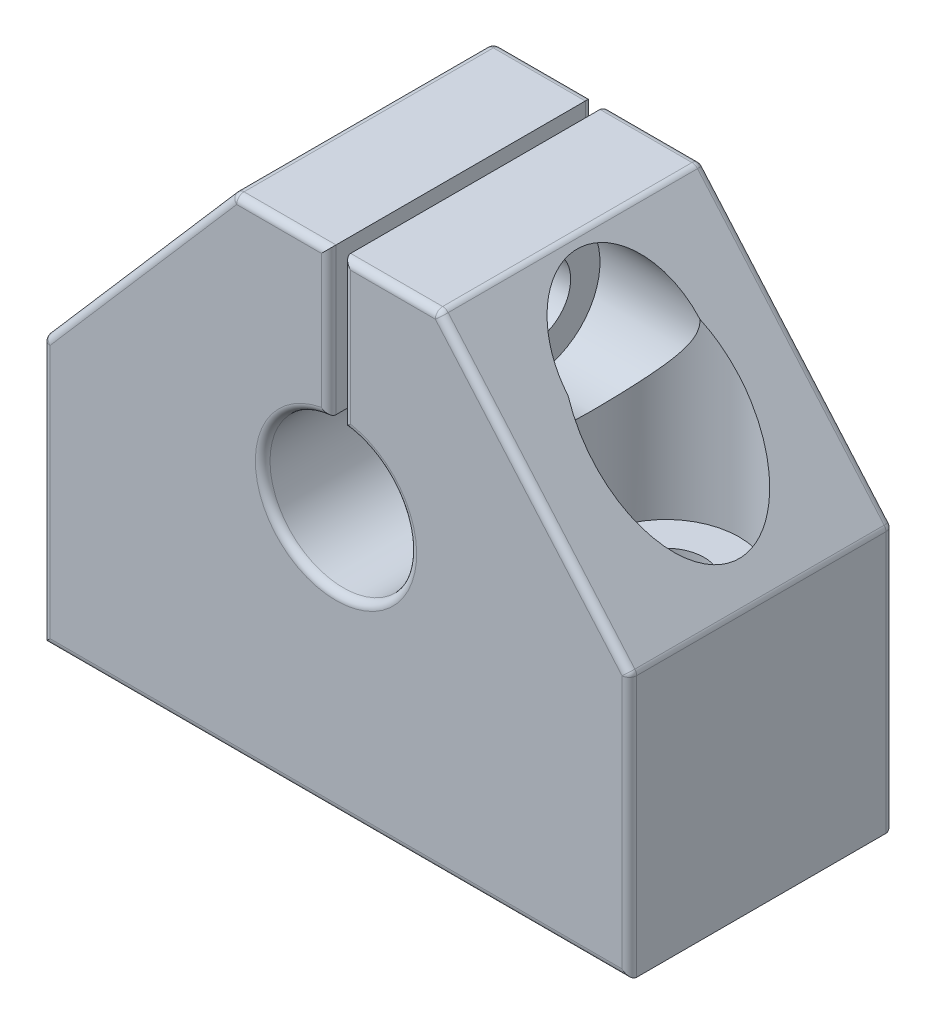
SolidWorks part; units mm, degrees
material "1060 Alloy"
ref_plane "Front Plane" through (0, 0, 0) normal (0, 0, 1) x (1, 0, 0)
ref_plane "Top Plane" through (0, 0, 0) normal (0, 1, 0) x (1, 0, 0)
ref_plane "Right Plane" through (0, 0, 0) normal (1, 0, 0) x (0, 0, -1)
sketch "Sketch1" plane through (0, 0, 0) normal (0, 0, 1) x (1, 0, 0)
  line L0 (20, 0) -> (20, 33) construction
  line L1 (0, 0) -> (40, 0)
  line L2 (0, 0) -> (0, 18)
  line L4 (40, 0) -> (40, 18)
  line L5 (13, 33) -> (0, 18)
  line L6 (13, 33) -> (27, 33)
  line L7 (27, 33) -> (40, 18)
  dimension "D1" = 18
  dimension "D2" = 40
  dimension "D3" = 33
  dimension "D5" = 7
extrude "Boss-Extrude1" add sketch "Sketch1" along normal blind 9 and the other way blind 9
sketch "Sketch2" plane through (0, 0, 9) normal (0, 0, 1) x (1, 0, 0)
  line L0 (20, 0) -> (20, 33) construction
  line L1 (0, 0) -> (40, 0) construction
  line L2 (27, 33) -> (13, 33) construction
  circle A0 centre (20, 18) radius 5
  dimension "D1" = 10
  dimension "D2" = 18
extrude "Cut-Extrude1" cut sketch "Sketch2" against normal through all
sketch "Sketch4" plane through (0, 0, 0) normal (0, 0, 1) x (1, 0, 0)
  line L0 (20, 0) -> (33.5, 0) construction
  line L1 (0, 0) -> (40, 0) construction
  dimension "D1" = 13.5
sketch "Sketch5" plane through (0, 0, 0) normal (0, -1, 0) x (-1, 0, 0)
  circle A0 centre (-33.5, 0) radius 2.6
  dimension "D1" = 5.2
extrude "Cut-Extrude2" cut sketch "Sketch5" against normal blind 16
sketch "Sketch7" plane through (0, 16, 0) normal (0, -1, 0) x (-1, 0, 0)
  circle A0 centre (-33.5, 0) radius 5
  dimension "D1" = 10
extrude "Cut-Extrude3" cut sketch "Sketch7" against normal through all
ref_plane "Plane1" through (20, 0, 0) normal (1, 0, 0) x (0, 0, -1)
mirror "Mirror1" about plane through (20, 0, 0) normal (1, 0, 0) of "Cut-Extrude2", "Cut-Extrude3"
sketch "Sketch9" plane through (0, 0, 9) normal (0, 0, 1) x (1, 0, 0)
  line L0 (20, 33) -> (20, 23) construction
  line L1 (27, 33) -> (13, 33) construction
  line L2 (20, -9.9) -> (20, 9.9) construction
  line L4 (19.5, 33.0251) -> (20.5, 33.0251)
  line L5 (19.5, 33.0251) -> (19.5, 22.9749)
  line L6 (19.5, 22.9749) -> (20.5, 22.9749)
  line L7 (20.5, 33.0251) -> (20.5, 22.9749)
  line L8 (19.5, 33.0251) -> (20.5, 22.9749) construction
  line L9 (19.5, 22.9749) -> (20.5, 33.0251) construction
  circle A0 centre (20, 18) radius 5 construction
  point P8 (20, 28)
  dimension "D1" = 1
extrude "Cut-Extrude4" cut sketch "Sketch9" against normal through all
sketch "Sketch10" plane through (19.5, 0, 0) normal (1, 0, 0) x (0, 0, -1)
  line L0 (0, 33) -> (0, 22.9749) construction
  line L1 (9, 33) -> (-9, 33) construction
  line L2 (9, 22.9749) -> (-9, 22.9749) construction
  circle A0 centre (0, 27.9875) radius 2.5
  dimension "D1" = 5
extrude "Cut-Extrude5" cut sketch "Sketch10" against normal through all and the other way blind 5
sketch "Sketch11" plane through (24.5, 0, 0) normal (-1, 0, 0) x (0, 0, 1)
  circle A0 centre (0, 27.9875) radius 4.5
  dimension "D1" = 9
extrude "Cut-Extrude6" cut sketch "Sketch11" against normal through all
fillet "Fillet1" radius 0.5 24 edges at (20, 13, -9) (19.5, 27.9875, -9) (16.25, 33, -9) (6.5, 25.5, -9) (0, 9, -9) (20, 0, -9) (40, 9, -9) (33.5, 25.5, -9) (23.75, 33, -9) (20.5, 27.9875, -9) (33.5, 25.5, 9) (40, 9, 9) (20, 0, 9) (0, 9, 9) (6.5, 25.5, 9) (16.25, 33, 9) (19.5, 27.9875, 9) (20, 13, 9) (20.5, 27.9875, 9) (23.75, 33, 9) (27, 33, 0) (13, 33, 0) (0, 18, 0) (40, 18, 0)
